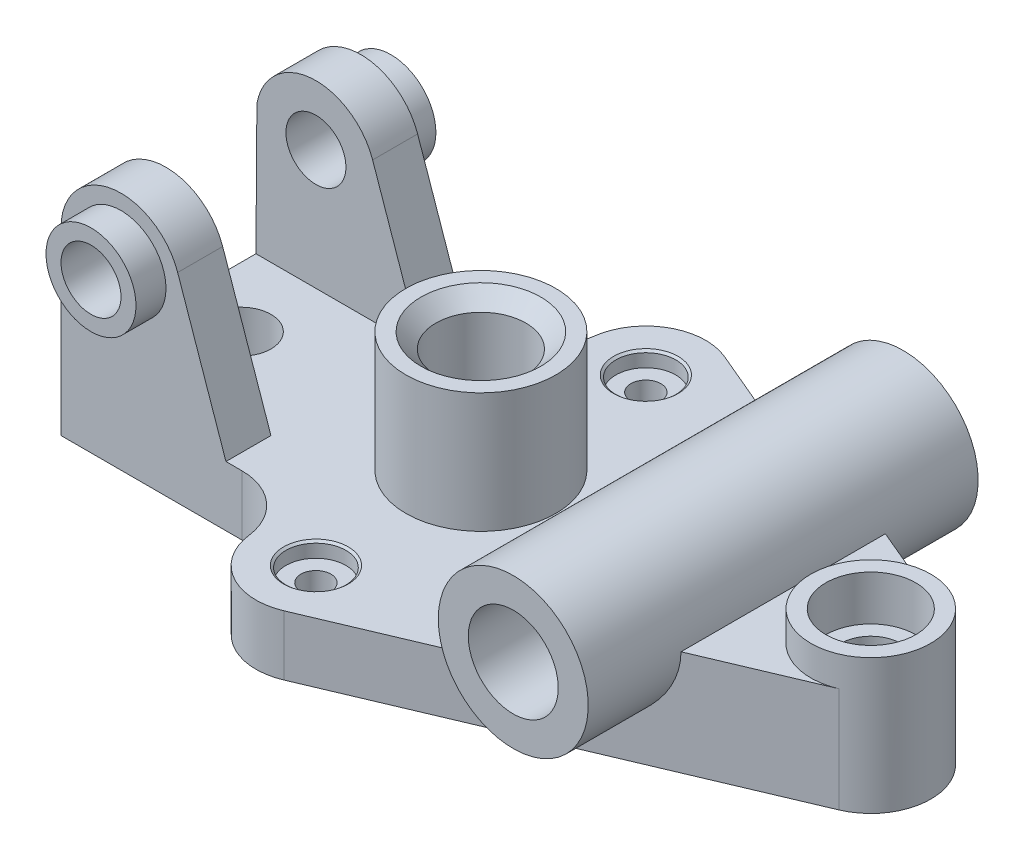
SolidWorks part; units mm, degrees
ref_plane "Front Plane" through (0, 0, 0) normal (0, 0, 1) x (1, 0, 0)
ref_plane "Top Plane" through (0, 0, 0) normal (0, 1, 0) x (1, 0, 0)
ref_plane "Right Plane" through (0, 0, 0) normal (1, 0, 0) x (0, 0, -1)
sketch "Sketch4" plane through (0, 0, 0) normal (0, 1, 0) x (1, 0, 0)
  line L0 (-77.2801, -56.6736) -> (-77.2801, 23.3264)
  line L1 (-77.2801, 23.3264) -> (-16.9664, 23.3264)
  line L2 (30.5127, 56.7457) -> (160.5127, 1.7457)
  line L3 (-77.2801, -16.6736) -> (152.7199, -16.6736) construction
  line L4 (30.5127, -90.0929) -> (160.5127, -35.0929)
  line L5 (-77.2801, -56.6736) -> (-16.9664, -56.6736)
  arc A0 (-16.9664, 23.3264) -> (2.8767, 40.8264) centre (-16.9664, 43.3264) ccw
  arc A1 (2.8767, 40.8264) -> (30.5127, 56.7457) centre (22.7199, 38.3264) cw
  arc A2 (160.5127, -35.0929) -> (160.5127, 1.7457) centre (152.7199, -16.6736) ccw
  circle A3 centre (-57.2801, -16.6736) radius 10
  arc A4 (2.8767, -74.1736) -> (30.5127, -90.0929) centre (22.7199, -71.6736) ccw
  arc A5 (-16.9664, -56.6736) -> (2.8767, -74.1736) centre (-16.9664, -76.6736) cw
  dimension "D2" = 20
  dimension "D5" = 20
  dimension "D6" = 20
  dimension "D7" = 80
  dimension "D8" = 40
  dimension "D1" = 40
  dimension "D3" = 210
  dimension "D4" = 20
  dimension "D9" = 55
extrude "Boss-Extrude1" add sketch "Sketch4" along normal blind 20
sketch "Sketch5" plane through (0, 0, 56.6736) normal (0, 0, 1) x (1, 0, 0)
  line L0 (-77.2801, 20) -> (-77.2801, 60)
  line L1 (-38.3791, 66.5384) -> (-22.2801, 20)
  line L2 (2.8767, 20) -> (-16.9664, 20) construction
  line L3 (-77.2801, 20) -> (-22.2801, 20)
  line L4 (-77.2801, 0) -> (-16.9664, 0) construction
  arc A0 (-77.2801, 60) -> (-38.3791, 66.5384) centre (-57.2801, 60) cw
  circle A1 centre (-57.2801, 60) radius 10
  dimension "D1" = 20
  dimension "D4" = 20
  dimension "D2" = 60
  dimension "D3" = 55
extrude "Boss-Extrude2" add sketch "Sketch5" against normal blind 15
sketch "Sketch6" plane through (0, 0, 56.6736) normal (0, 0, 1) x (1, 0, 0)
  circle A0 centre (-57.2801, 60) radius 15
  circle M8 centre (-57.2801, 60) radius 10
  dimension "D1" = 30
extrude "Boss-Extrude4" add sketch "Sketch6" along normal blind 10 contours M8 | A0 region at (-57.2801, 60, 56.6736)
sketch "Sketch10" plane through (0, 0, -23.3264) normal (0, 0, -1) x (-1, 0, 0)
  line L0 (22.2801, 20) -> (38.3791, 66.5384)
  line L1 (76.969, 63.514) -> (77.2801, 20)
  line L2 (77.2801, 20) -> (22.2801, 20)
  arc A0 (38.3791, 66.5384) -> (76.969, 63.514) centre (57.2801, 60) cw
  arc A1 (77.2801, 60) -> (38.3791, 66.5384) centre (57.2801, 60) ccw construction
  circle A2 centre (57.2801, 60) radius 10
  dimension "D1" = 20
extrude "Boss-Extrude6" add sketch "Sketch10" against normal blind 15
sketch "Sketch11" plane through (0, 0, -23.3264) normal (0, 0, -1) x (-1, 0, 0)
  circle A0 centre (57.2801, 60) radius 15
  circle M8 centre (57.2801, 60) radius 10
  dimension "D1" = 30
extrude "Boss-Extrude7" add sketch "Sketch11" along normal blind 10 contours A0 M8 region at (-42.7044, 60, -23.3264)
hole_wizard "CBORE for M10 Hex Head Bolt2" positions "3DSketch2" profile "Sketch16" counterbore size "M10" standard "ISO" end condition through all
sketch3d "3DSketch2"
  line L0 (22.7199, 20, -38.3264) -> (22.7199, 0, -38.3264) construction
  line L1 (22.7199, 20, 71.6736) -> (22.7199, 0, 71.6736) construction
  point P0 (-2.6719, 0, -390.0034)
  point P2 (22.7199, 20, -38.3264)
  point P6 (22.7199, 20, 71.6736)
sketch "Sketch16" plane through (22.7199, 20, 71.6736) normal (1, 0, 0) x (0, 0, 1)
  line L0 (0, 0) -> (0, 20)
  line L1 (0, 20) -> (5, 20)
  line L3 (5, 20) -> (5, 5)
  line L4 (10, 5) -> (5, 5)
  line L5 (10, 5) -> (10, 0.6398)
  line L6 (10, 0.6398) -> (10.7625, 0)
  line L7 (10.7625, 0) -> (0, 0)
  line L8 (-10, 0.6398) -> (-10.7625, 0) construction
  line L11 (0, -6.35) -> (0, 107.95) construction
  dimension "Thru Hole Dia." = 10
  dimension "Thru Hole Depth" = 20
  dimension "C'Bore Dia." = 20
  dimension "C'Bore Depth" = 5
  dimension "Near C'Sink Dia." = 21.525
  dimension "Near C'Sink Angle" = 100
sketch "Sketch12" plane through (0, 20, 0) normal (0, 1, 0) x (1, 0, 0)
  line L0 (-77.2801, -16.6736) -> (172.7199, -16.6736) construction
  line L1 (-77.2801, 8.3264) -> (-77.2801, -41.6736) construction
  arc A0 (160.5127, -35.0929) -> (160.5127, 1.7457) centre (152.7199, -16.6736) ccw construction
  circle A1 centre (22.7199, -16.6736) radius 25
  circle A2 centre (-57.2801, -16.6736) radius 10 construction
  dimension "D1" = 80
  dimension "D2" = 50
extrude "Boss-Extrude8" add sketch "Sketch12" along normal blind 40 and the other way blind 35
hole_wizard "CSK for M10 Countersunk Flat Head Screw1" positions "3DSketch3" profile "Sketch18" countersink size "M10" standard "ISO" end condition through all
sketch3d "3DSketch3"
  line L0 (22.7199, 20, 16.6736) -> (22.7199, 60, 16.6736) construction
  point P0 (22.7199, 60, 16.6736)
sketch "Sketch18" plane through (22.7199, 60, 16.6736) normal (1, 0, 0) x (0, 0, 1)
  line L0 (0, 0) -> (0, 75)
  line L1 (0, 75) -> (20, 75)
  line L2 (15, 70) -> (15, 5)
  line L3 (15, 5) -> (20, 0)
  line L5 (20, 0) -> (0, 0)
  line L6 (-15, 5) -> (-20, 0) construction
  line L7 (20, 75) -> (15, 70)
  line L8 (-20, 75) -> (-15, 70) construction
  line L11 (0, -6.35) -> (0, 107.95) construction
  dimension "Thru Hole Dia." = 30
  dimension "Thru Hole Depth" = 75
  dimension "Near C'Sink Dia." = 40
  dimension "Near C'Sink Angle" = 90
  dimension "Far C'Sink Dia." = 40
  dimension "Far C'Sink Angle" = 90
sketch "Sketch19" plane through (0, 20, 0) normal (0, 1, 0) x (1, 0, 0)
  circle A0 centre (152.7199, -16.6736) radius 20
extrude "Boss-Extrude9" add sketch "Sketch19" along normal blind 25
hole_wizard "CBORE for M10 Hex Head Bolt3" positions "3DSketch4" profile "Sketch20" counterbore size "M10" standard "ISO" end condition through all
sketch3d "3DSketch4"
  line L0 (152.7199, 20, 16.6736) -> (152.7199, 0, 16.6736) construction
  point P0 (152.7199, 45, 16.6736)
sketch "Sketch20" plane through (152.7199, 45, 16.6736) normal (1, 0, 0) x (0, 0, 1)
  line L0 (0, 0) -> (0, 45)
  line L1 (10, 35) -> (20, 45)
  line L2 (10, 35) -> (10, 15)
  line L3 (10, 15) -> (15, 15)
  line L4 (15, 15) -> (15, 0)
  line L5 (15, 0) -> (0, 0)
  line L11 (0, -6.35) -> (0, 107.95) construction
  line L12 (20, 45) -> (0, 45)
  line L13 (-10, 35) -> (-20, 45) construction
  dimension "Thru Hole Dia." = 20
  dimension "Thru Hole Depth" = 45
  dimension "C'Bore Dia." = 30
  dimension "C'Bore Depth" = 15
  dimension "Far C'Sink Dia." = 40
  dimension "Far C'Sink Angle" = 90
sketch "Sketch23" plane through (0, 20, 0) normal (0, 1, 0) x (1, 0, 0)
  line L0 (160.5127, 1.7457) -> (72.7199, 38.8889)
  line L1 (160.5127, 1.7457) -> (30.5127, 56.7457) construction
  line L2 (72.7199, 38.8889) -> (72.7199, -72.2361)
  line L3 (30.5127, -90.0929) -> (160.5127, -35.0929) construction
  line L4 (72.7199, -72.2361) -> (160.5127, -35.0929)
  arc A0 (160.5127, -35.0929) -> (160.5127, 1.7457) centre (152.7199, -16.6736) ccw
  line M8 (30.5127, -90.0929) -> (160.5127, -35.0929)
  arc M9 (160.5127, -35.0929) -> (160.5127, 1.7457) centre (152.7199, -16.6736) cw
  line M10 (160.5127, 1.7457) -> (30.5127, 56.7457)
  dimension "D1" = 80
extrude "Boss-Extrude10" add sketch "Sketch23" along normal blind 15 contours L2 M10 M8 M9 region at (102.7401, 20, 16.6736)
ref_plane "Plane1" through (0, 0, 16.6736) normal (0, 0, -1) x (-1, 0, 0)
sketch "Sketch28" plane through (0, 0, 16.6736) normal (0, 0, -1) x (-1, 0, 0)
  line L0 (-160.5127, 35) -> (-72.7199, 35) construction
  line L1 (-160.5127, 0) -> (-30.5127, 0) construction
  line L3 (-132.7199, 45) -> (-172.7199, 45) construction
  line L4 (-153.5119, 45) -> (-153.5119, -26.6885) construction
  circle A0 centre (-98.5119, 35) radius 25
  dimension "D1" = 50
  dimension "D2" = 35
  dimension "D3" = 55
extrude "Boss-Extrude14" add sketch "Sketch28" along normal blind 65 and the other way blind 65
sketch "Sketch29" plane through (0, 0, -48.3264) normal (0, 0, -1) x (-1, 0, 0)
  circle A0 centre (-98.5119, 35) radius 15
  dimension "D1" = 30
extrude "Cut-Extrude2" cut sketch "Sketch29" against normal blind 181
